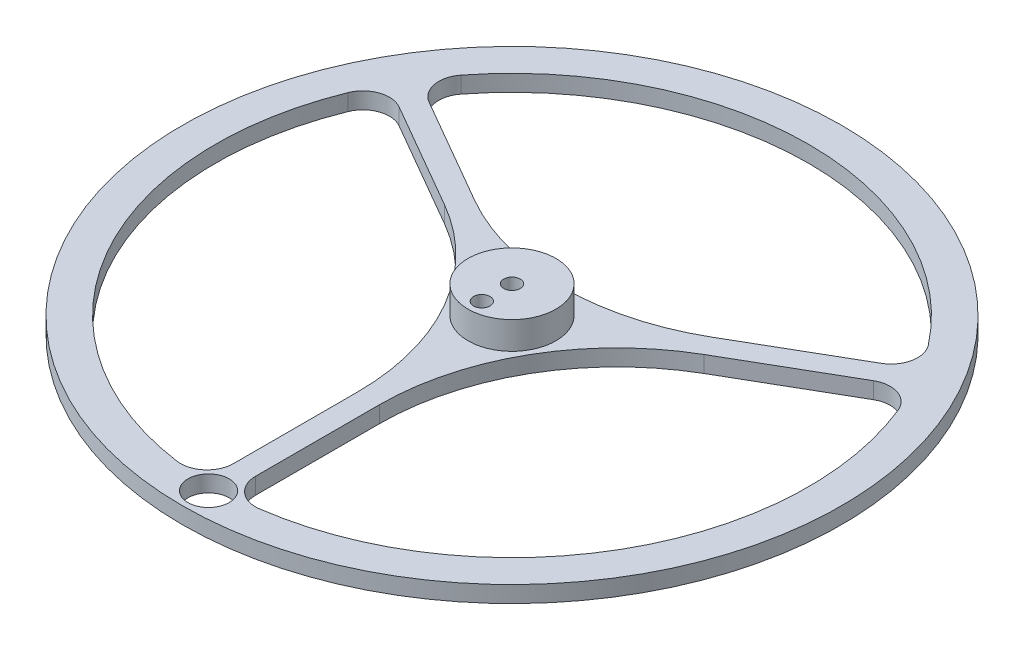
SolidWorks part; units mm, degrees
ref_plane "Front Plane" through (0, 0, 0) normal (0, 0, 1) x (1, 0, 0)
ref_plane "Top Plane" through (0, 0, 0) normal (0, 1, 0) x (1, 0, 0)
ref_plane "Right Plane" through (0, 0, 0) normal (1, 0, 0) x (0, 0, -1)
sketch "Sketch1" plane through (0, 0, 0) normal (0, 1, 0) x (1, 0, 0)
  line L0 (2, -48.6942) -> (2, -26.1244)
  line L1 (23.6244, 11.3301) -> (43.1704, 22.615)
  line L2 (21.6244, 14.7942) -> (41.1704, 26.0791)
  line L3 (-2, -26.1244) -> (-2, -48.6942)
  line L4 (-2, -26.1244) -> (2, -26.1244) construction
  line L5 (0, -9) -> (0, 9) construction
  line L6 (0, -60) -> (0, 9) construction
  line L7 (-41.1704, 26.0791) -> (-21.6244, 14.7942)
  line L8 (-43.1704, 22.615) -> (-23.6244, 11.3301)
  line L9 (-11.0325, 9) -> (11.0325, 9) construction
  line L10 (0, 9) -> (0, 10.9405) construction
  line L12 (0, -26.1244) -> (0, -9) construction
  line L13 (-7.5, -53.4766) -> (7.5, -53.4766) construction
  line L14 (0, -60) -> (0, -53.4766) construction
  circle A0 centre (0, 0) radius 60
  circle A1 centre (0, 0) radius 54
  circle A2 centre (0, 0) radius 8
  arc A3 (-21.6244, 14.7942) -> (0, 9) centre (0, 52.2487) ccw
  arc A4 (0, 9) -> (21.6244, 14.7942) centre (0, 52.2487) ccw
  arc A5 (-2, -48.6942) -> (-7.5, -53.4766) centre (-6.8293, -48.6942) cw
  arc A6 (2, -48.6942) -> (7.5, -53.4766) centre (6.8293, -48.6942) ccw
  arc A7 (-41.1704, 26.0791) -> (-42.5621, 33.2335) centre (-38.7558, 30.2614) cw
  arc A8 (-43.1704, 22.615) -> (-50.0621, 20.2431) centre (-45.585, 18.4328) ccw
  arc A9 (43.1704, 22.615) -> (50.0621, 20.2431) centre (45.585, 18.4328) cw
  arc A10 (41.1704, 26.0791) -> (42.5621, 33.2335) centre (38.7558, 30.2614) ccw
  arc A11 (23.6244, 11.3301) -> (7.7942, -4.5) centre (45.2487, -26.1244) ccw
  arc A12 (7.7942, -4.5) -> (2, -26.1244) centre (45.2487, -26.1244) ccw
  arc A13 (-2, -26.1244) -> (-7.7942, -4.5) centre (-45.2487, -26.1244) ccw
  arc A14 (-7.7942, -4.5) -> (-23.6244, 11.3301) centre (-45.2487, -26.1244) ccw
  dimension "D1" = 6
  dimension "D5" = 16
  dimension "D9" = 120
  dimension "D2" = 69
  dimension "D3" = 3
  dimension "D4" = 4
  dimension "D10" = 15
extrude "Boss-Extrude1" add sketch "Sketch1" against normal blind 3 contours A0 A1 | A14 A13 L3 A5 A1 A6 L0 A12 A11 L1 A9 A10 L2 A4 A3 L7 A7 A8 L8 A2 | A2 region at (2.7891, 0, 53.3405) region at (-58.3029, 0, 0) region at (0, 0, 0)
extrude "Boss-Extrude2" add sketch "Sketch1<3>" along normal blind 5 contours A2 region at (0, 0, 0)
sketch "Sketch1<3>" plane through (0, 0, 0) normal (0, 1, 0) x (1, 0, 0) same geometry as "Sketch1"
sketch "Sketch2" plane through (0, 5, 0) normal (0, 1, 0) x (1, 0, 0)
  circle A0 centre (0, 0) radius 1.5
  dimension "D1" = 3
extrude "Cut-Extrude1" cut sketch "Sketch2" against normal up to next
sketch "Sketch3" plane through (0, 0, 0) normal (0, 1, 0) x (1, 0, 0)
  line L0 (0, 0) -> (0, -55.25) construction
  circle A0 centre (0, -55.25) radius 3.75
  dimension "D1" = 7.5
  dimension "D2" = 55.25
extrude "Cut-Extrude2" cut sketch "Sketch3" against normal up to next
sketch "Sketch4" plane through (0, 5, 0) normal (0, 1, 0) x (1, 0, 0)
  line L0 (0, 0) -> (0, -5.5) construction
  circle A0 centre (0, -5.5) radius 1.5
  dimension "D2" = 3
  dimension "D1" = 5.5
extrude "Cut-Extrude3" cut sketch "Sketch4" against normal up to surface (5 mm away) up to face at (0, 0, 59)
